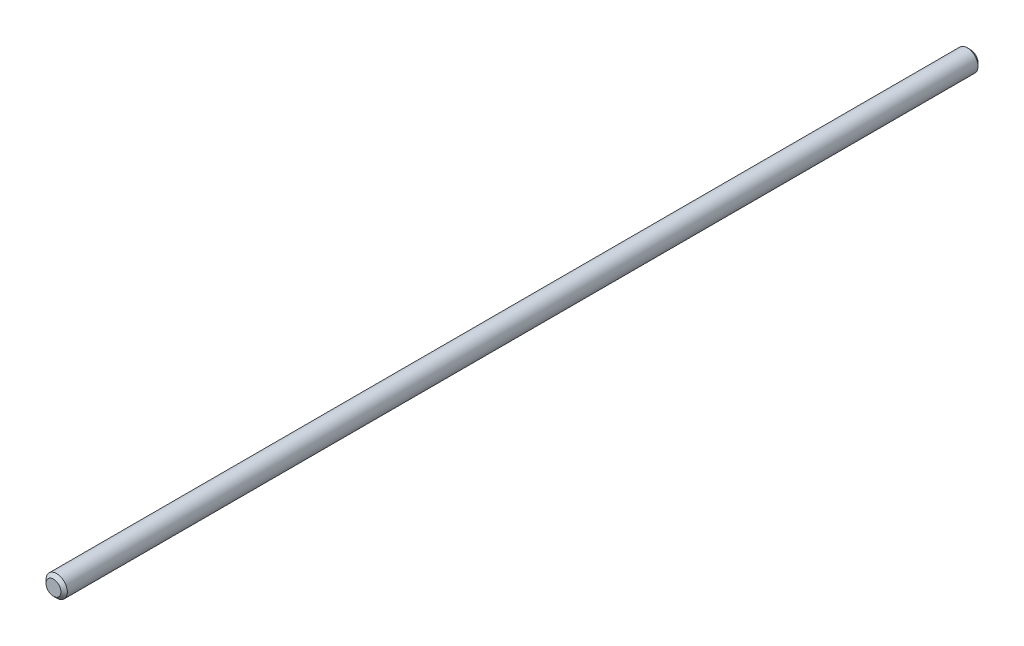
SolidWorks part; units mm, degrees
ref_plane "Front Plane" through (0, 0, 0) normal (0, 0, 1) x (1, 0, 0)
ref_plane "Top Plane" through (0, 0, 0) normal (0, 1, 0) x (1, 0, 0)
ref_plane "Right Plane" through (0, 0, 0) normal (1, 0, 0) x (0, 0, -1)
sketch "Sketch1" plane through (0, 0, 0) normal (1, 0, 0) x (0, 0, -1)
  line L0 (136.525, 0) -> (-136.525, 0) construction
  line L1 (136.525, 3.175) -> (136.525, -3.175) construction
  line L2 (-136.525, 3.175) -> (-136.525, -3.175) construction
  line L3 (136.525, 3.175) -> (137.795, 3.175) construction
  line L4 (136.525, -3.175) -> (219.075, -3.175) construction
  line L5 (-136.525, -3.175) -> (-139.7, -3.175) construction
  point P0 (146.05, 0)
  point P4 (0, 0)
  point P8 (136.525, 0)
  point P11 (-136.525, 0)
  point P16 (219.075, -3.175)
  point P19 (-136.525, -3.175)
  point P21 (-146.05, 0)
  point P22 (-139.7, -3.175)
  dimension "Thread Diameter" = 6.35
  dimension "Length" = 273.05
  dimension "Thread Pitch" = 1.27
  dimension "Segment Length" = 82.55
  dimension "D1" = 9.525
  dimension "D4" = 9.525
  dimension "D5" = 3.175
sketch "Sketch2" plane through (0, 0, 0) normal (0, 0, 1) x (1, 0, 0)
  line L0 (0, 3.175) -> (0, -3.175) construction
  circle A0 centre (0, 0) radius 3.175
extrude "Boss-Extrude1" add sketch "Sketch2" along normal up to vertex (-136.525 mm away) and the other way up to vertex (-136.525 mm away) up to point (0, 0, -136.525) other way up to point (0, 0, 136.525)
chamfer "Chamfer1" distance 0.9525 angle 45 2 edges at (3.175, 0, 136.525) (3.175, 0, -136.525)
sketch "Sketch4" [suppressed] plane through (0, 0, 152.4) normal (0, 0, 1) x (1, 0, 0)
  circle A0 centre (0, 0) radius 3.175 construction
  circle A1 centre (0, 0) radius 3.175
curve "Helix/Spiral1" [suppressed] pitch 1.27 height 83.82 turns 66
sketch "Sketch5" [suppressed] plane through (0, 0, 0) normal (1, 0, 0) x (0, 0, -1)
  line L0 (-153.5906, 3.3125) -> (-152.3206, 3.3125) construction
  line L1 (-152.3206, 3.3125) -> (-152.9556, 2.2126) construction
  line L2 (-152.9556, 2.2126) -> (-153.5906, 3.3125) construction
  line L3 (-152.9556, 2.2126) -> (-152.9556, 2.3501) construction
  line L4 (-153.035, 2.3501) -> (-152.8762, 2.3501)
  line L5 (-152.9556, 3.3125) -> (-152.9556, 3.175) construction
  line L6 (-153.5509, 3.2437) -> (-152.3603, 3.2437)
  line L7 (-152.3603, 3.2437) -> (-152.8762, 2.3501)
  line L8 (-153.5509, 3.2437) -> (-153.035, 2.3501)
  line L9 (-153.5112, 3.175) -> (-152.4, 3.175) construction
  line L10 (-152.4, 3.175) -> (-151.13, 3.175) construction
  point P2 (-152.9556, 3.3125)
  point P8 (-152.9556, 2.3501)
  point P14 (-152.9556, 3.2437)
  point P16 (-152.9556, 3.175)
  dimension "D2" = 0.1588
sweep "Cut-Sweep1" [suppressed] cut profiles "Sketch5" path "Helix/Spiral1"
pattern_linear "LPattern1" [suppressed] count 4 spacing 81.28 along (0, 0, 1) of bodies 105
equation "\"Segment Length@Sketch1\"=\"Thread Pitch@Sketch1\"*65"
equation "\"D1@Chamfer1\"=\"Thread Pitch@Sketch1\"*.75"
equation "\"D4@Helix/Spiral1\"=\"Thread Pitch@Sketch1\""
equation "\"D3@Helix/Spiral1\"=\"Segment Length@Sketch1\"+\"Thread Pitch@Sketch1\""
equation "\"D2@Sketch5\"=\"Thread Pitch@Sketch1\"*.125"
equation "\"D1@LPattern1\"=(\"Length@Sketch1\"/(\"Segment Length@Sketch1\"-\"Thread Pitch@Sketch1\"))+1"
equation "\"D3@LPattern1\"=\"Segment Length@Sketch1\"-\"Thread Pitch@Sketch1\""
equation "\"D4@Sketch1\"=\"D1@Sketch1\""
equation "\"D5@Sketch1\"=\"Thread Pitch@Sketch1\"*2.5"
equation "\"D1@Sketch1\"=\"Thread Diameter@Sketch1\"*1.5"
equation "\"Length@Sketch1\"=12-2.08+0.5+(9-8.67)"
